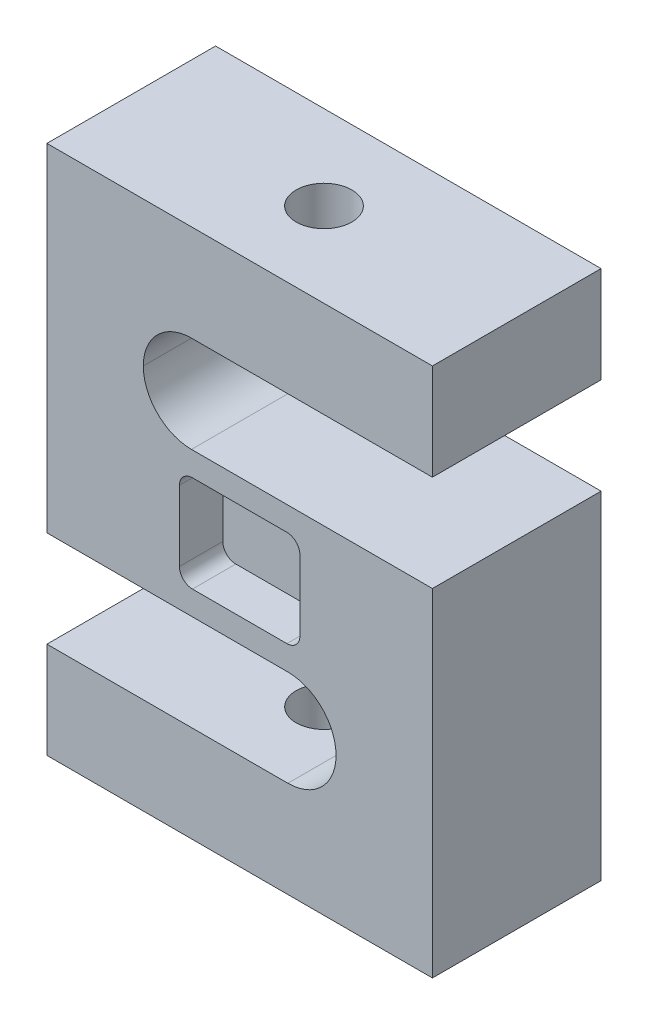
SolidWorks part; units mm, degrees
material "Plain Carbon Steel"
ref_plane "Front Plane" through (0, 0, 0) normal (0, 0, 1) x (1, 0, 0)
ref_plane "Top Plane" through (0, 0, 0) normal (0, 1, 0) x (1, 0, 0)
ref_plane "Right Plane" through (0, 0, 0) normal (1, 0, 0) x (0, 0, -1)
sketch "Sketch1" plane through (0, 0, 0) normal (0, 0, 1) x (1, 0, 0)
  line L0 (76.2, 0) -> (0, 0)
  line L1 (76.2, 0) -> (76.2, -88.9)
  line L2 (76.2, -88.9) -> (-25.4, -88.9)
  line L3 (-25.4, -88.9) -> (-25.4, -63.5)
  line L4 (-25.4, -63.5) -> (50.8, -63.5)
  line L5 (50.8, -63.5) -> (50.8, -38.1)
  line L6 (50.8, -38.1) -> (-25.4, -38.1)
  line L7 (-25.4, -38.1) -> (-25.4, 50.8)
  line L8 (-25.4, 50.8) -> (76.2, 50.8)
  line L9 (76.2, 50.8) -> (76.2, 25.4)
  line L10 (76.2, 25.4) -> (0, 25.4)
  line L11 (0, 25.4) -> (0, 0)
  dimension "D1" = 139.7
  dimension "D2" = 25.4
  dimension "D4" = 25.4
  dimension "D5" = 101.6
extrude "Boss-Extrude1" add sketch "Sketch1" along normal mid plane 44.45
fillet "Fillet1" radius 12.7 4 edges at (50.8, -63.5, 0) (50.8, -38.1, 0) (0, 25.4, 0) (0, 0, 0)
sketch "Sketch2" plane through (0, 50.8, 0) normal (0, 1, 0) x (1, 0, 0)
  line L0 (25.4, 22.225) -> (25.4, -22.225) construction
  line L1 (76.2, 22.225) -> (-25.4, 22.225) construction
  line L2 (76.2, -22.225) -> (-25.4, -22.225) construction
  point P6 (25.4, 0)
sketch "Sketch3" plane through (0, -88.9, 0) normal (0, -1, 0) x (1, 0, 0)
  line L0 (25.4, 22.225) -> (25.4, -22.225) construction
  line L1 (-25.4, 22.225) -> (76.2, 22.225) construction
  line L2 (-25.4, -22.225) -> (76.2, -22.225) construction
  point P6 (25.4, 0)
hole_wizard "5/8-18 Tapped Hole1" positions "Sketch5" profile "Sketch4" tap size "5/8-18" standard "Ansi Inch" end condition up to next
sketch "Sketch5" plane through (0, -88.9, 0) normal (0, -1, 0) x (1, 0, 0)
  point P1 (25.4, 0)
sketch "Sketch4" plane through (25.4, -88.9, 0) normal (1, 0, 0) x (0, 0, -1)
  line L0 (0, 0) -> (0, 25.4)
  line L1 (0, 25.4) -> (7.3419, 25.4)
  line L2 (7.3419, 25.4) -> (7.3419, 0)
  line L5 (7.3419, 0) -> (0, 0)
  line L11 (0, -6.35) -> (0, 107.95) construction
  dimension "Thru Tap Drill Dia." = 14.6837
  dimension "Thru Tap Drill Depth" = 25.4
cosmetic thread "Hole Thread3" parameters "D1"=0, "D2"=24.6837
hole_wizard "5/8-18 Tapped Hole2" positions "Sketch7" profile "Sketch6" tap size "5/8-18" standard "Ansi Inch" end condition up to next
sketch "Sketch7" plane through (0, 50.8, 0) normal (0, 1, 0) x (-1, 0, 0)
  point P1 (-25.4, 0)
sketch "Sketch6" plane through (25.4, 50.8, 0) normal (1, 0, 0) x (0, 0, 1)
  line L0 (0, 0) -> (0, 25.4)
  line L1 (0, 25.4) -> (7.3419, 25.4)
  line L2 (7.3419, 25.4) -> (7.3419, 0)
  line L5 (7.3419, 0) -> (0, 0)
  line L11 (0, -6.35) -> (0, 107.95) construction
  dimension "Thru Tap Drill Dia." = 14.6837
  dimension "Thru Tap Drill Depth" = 25.4
cosmetic thread "Hole Thread4" parameters "D1"=0, "D2"=24.6837
sketch "Sketch8" plane through (0, 0, 22.225) normal (0, 0, 1) x (1, 0, 0)
  line L0 (25.4, 50.8) -> (25.4, -6.35) construction
  line L1 (9.525, -31.75) -> (41.275, -31.75)
  line L2 (9.525, -31.75) -> (9.525, -6.35)
  line L3 (9.525, -6.35) -> (41.275, -6.35)
  line L4 (41.275, -31.75) -> (41.275, -6.35)
  line L5 (9.525, -31.75) -> (41.275, -6.35) construction
  line L6 (9.525, -6.35) -> (41.275, -31.75) construction
  line L7 (76.2, 50.8) -> (-25.4, 50.8) construction
  line L8 (41.275, -6.35) -> (41.275, 0) construction
  line L9 (76.2, 0) -> (12.7, 0) construction
  line L10 (9.525, -31.75) -> (9.525, -38.1) construction
  line L11 (-25.4, -38.1) -> (38.1, -38.1) construction
  point P0 (25.4, -19.05)
  dimension "D1" = 25.4
  dimension "D2" = 31.75
extrude "Cut-Extrude1" cut sketch "Sketch8" against normal blind 11.43
fillet "Fillet2" radius 3.429 4 edges at (9.525, -31.75, 16.51) (41.275, -31.75, 16.51) (41.275, -6.35, 16.51) (9.525, -6.35, 16.51)
mirror "Mirror1" about plane through (0, 0, 0) normal (0, 0, 1) of "Fillet2", "Cut-Extrude1"
